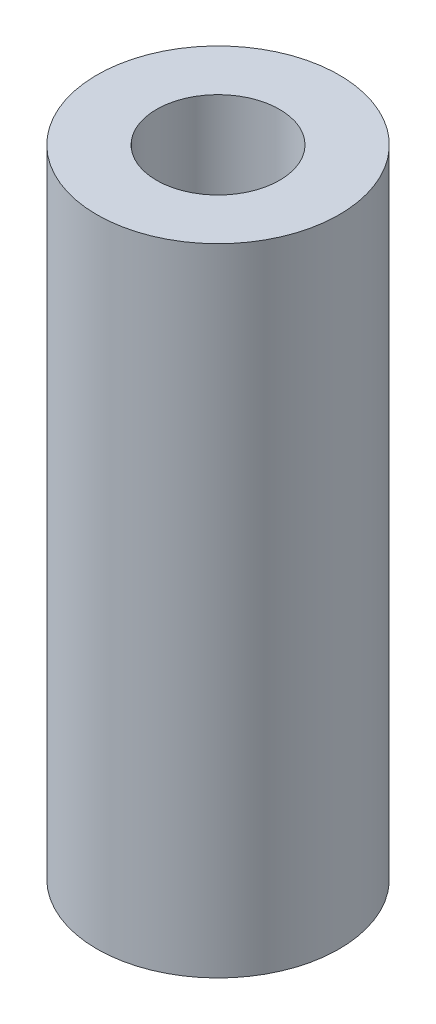
SolidWorks part; units mm, degrees
ref_plane "Front Plane" through (0, 0, 0) normal (0, 0, 1) x (1, 0, 0)
ref_plane "Top Plane" through (0, 0, 0) normal (0, 1, 0) x (1, 0, 0)
ref_plane "Right Plane" through (0, 0, 0) normal (1, 0, 0) x (0, 0, -1)
sketch "Sketch1" plane through (0, 0, 0) normal (0, 1, 0) x (1, 0, 0)
  circle A0 centre (0, 0) radius 6.35
  arc A4 (2.3664, 5.8926) -> (-4.4843, -4.4959) centre (0, 0) ccw construction
  circle A5 centre (0, 0) radius 3.2258
  circle A6 centre (0, 0) radius 3.2258
  dimension "D1" = 0.0508
extrude "Boss-Extrude1" add sketch "Sketch1" along normal up to surface (33.3375 mm away)
